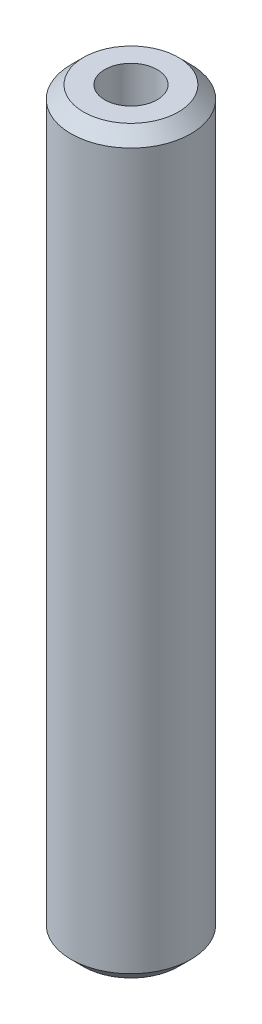
SolidWorks part; units mm, degrees
ref_plane "Front Plane" through (0, 0, 0) normal (0, 0, 1) x (1, 0, 0)
ref_plane "Top Plane" through (0, 0, 0) normal (0, 1, 0) x (1, 0, 0)
ref_plane "Right Plane" through (0, 0, 0) normal (1, 0, 0) x (0, 0, -1)
sketch "Sketch1" plane through (0, 0, 0) normal (0, 1, 0) x (1, 0, 0)
  circle A0 centre (0, 0) radius 10
  dimension "SHAFT_OD" = 20
extrude "Boss-Extrude1" add sketch "Sketch1" along normal blind 123.483
sketch "Sketch2" plane through (0, 0, 0) normal (0, 1, 0) x (1, 0, 0)
  circle A0 centre (0, 0) radius 4.3761
  dimension "BORE_D" = 8.7523
extrude "Cut-Extrude1" cut sketch "Sketch2" along normal through all
chamfer "Chamfer1" distance 2.0968 angle 45 2 edges at (0, 123.483, 10) (0, 0, 10)
